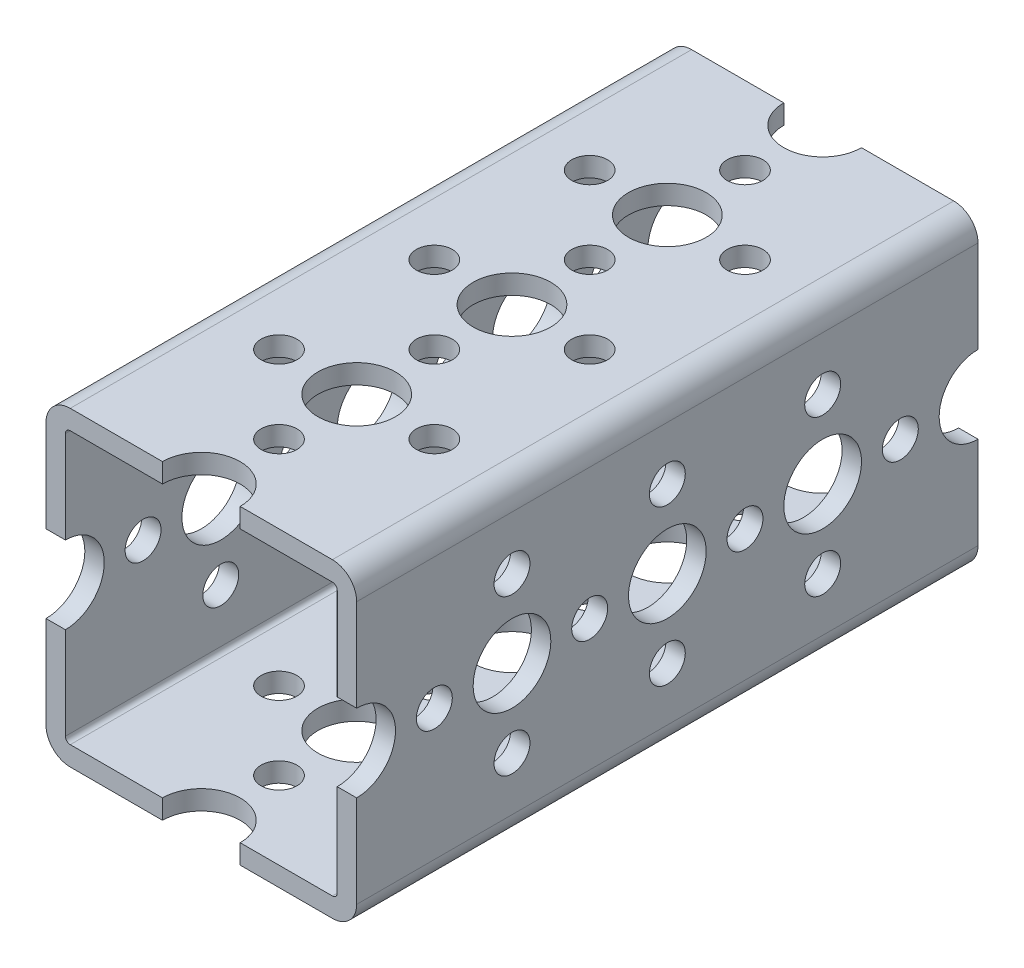
SolidWorks part; units mm, degrees
ref_plane "Front Plane" through (0, 0, 0) normal (0, 0, 1) x (1, 0, 0)
ref_plane "Top Plane" through (0, 0, 0) normal (0, 1, 0) x (1, 0, 0)
ref_plane "Right Plane" through (0, 0, 0) normal (1, 0, 0) x (0, 0, -1)
sketch "Sketch1" plane through (0, 0, 0) normal (0, 0, 1) x (1, 0, 0)
  line L0 (-16, 16) -> (16, -16) construction
  line L1 (-13.5, 16) -> (13.5, 16)
  line L2 (-16, 13.5) -> (-16, -13.5)
  line L3 (-13.5, -16) -> (13.5, -16)
  line L4 (16, 13.5) -> (16, -13.5)
  line L5 (-13.5, 14) -> (13.5, 14)
  line L6 (14, 13.5) -> (14, -13.5)
  line L7 (-13.5, -14) -> (13.5, -14)
  line L8 (-14, 13.5) -> (-14, -13.5)
  arc A0 (-16, -13.5) -> (-13.5, -16) centre (-13.5, -13.5) ccw
  arc A1 (13.5, -16) -> (16, -13.5) centre (13.5, -13.5) ccw
  arc A2 (16, 13.5) -> (13.5, 16) centre (13.5, 13.5) ccw
  arc A3 (-13.5, 16) -> (-16, 13.5) centre (-13.5, 13.5) ccw
  arc A4 (14, 13.5) -> (13.5, 14) centre (13.5, 13.5) ccw
  arc A5 (13.5, -14) -> (14, -13.5) centre (13.5, -13.5) ccw
  arc A6 (-14, -13.5) -> (-13.5, -14) centre (-13.5, -13.5) ccw
  arc A7 (-13.5, 14) -> (-14, 13.5) centre (-13.5, 13.5) ccw
  dimension "D1" = 2.5
  dimension "D4" = 0.5
  dimension "D2" = 32
  dimension "D3" = 2
  dimension "D5" = 2
extrude "Boss-Extrude1" add sketch "Sketch1" along normal mid plane 64
sketch "Sketch2" plane through (16, 0, 0) normal (1, 0, 0) x (0, 0, -1)
  line L0 (32, -13.5) -> (32, 13.5) construction
  line L1 (0, 0) -> (-16, 0) construction
  line L2 (-16, 0) -> (-32, 0) construction
  line L3 (0, 0) -> (16, 0) construction
  line L4 (16, 0) -> (32, 0) construction
  line L5 (16, 0) -> (16, 8) construction
  line L6 (16, 0) -> (16, -8) construction
  line L7 (-32, -13.5) -> (-32, 13.5) construction
  circle A0 centre (0, 0) radius 4
  circle A1 centre (16, 0) radius 4
  circle A2 centre (32, 0) radius 4
  circle A3 centre (-16, 0) radius 4
  circle A4 centre (-32, 0) radius 4
  circle A5 centre (24, 0) radius 1.85
  circle A6 centre (16, 8) radius 1.85
  circle A7 centre (16, -8) radius 1.85
  circle A8 centre (8, 0) radius 1.85
  circle A9 centre (-8, 0) radius 1.85
  circle A10 centre (-24, 0) radius 1.85
  circle A11 centre (-32, 8) radius 1.85 construction
  circle A12 centre (-32, -8) radius 1.85 construction
  circle A13 centre (-16, -8) radius 1.85
  circle A14 centre (-16, 8) radius 1.85
  circle A15 centre (0, 8) radius 1.85
  circle A16 centre (0, -8) radius 1.85
  circle A17 centre (32, -8) radius 1.85 construction
  circle A18 centre (32, 8) radius 1.85 construction
  dimension "D2" = 8
  dimension "D3" = 3.7
  dimension "D1" = 16
  dimension "D4" = 16
extrude "Cut-Extrude1" cut sketch "Sketch2" against normal through all
ref_axis "Axis1" through (0, 0, -17.6) along (0, 0, 1)
pattern_circular "CirPattern1" count 2 over 90 about axis through (0, 0, -17.6) along (0, 0, 1) of "Cut-Extrude1"
ref_axis "Axis2" through (14, 0, -16) along (1, 0, 0)
